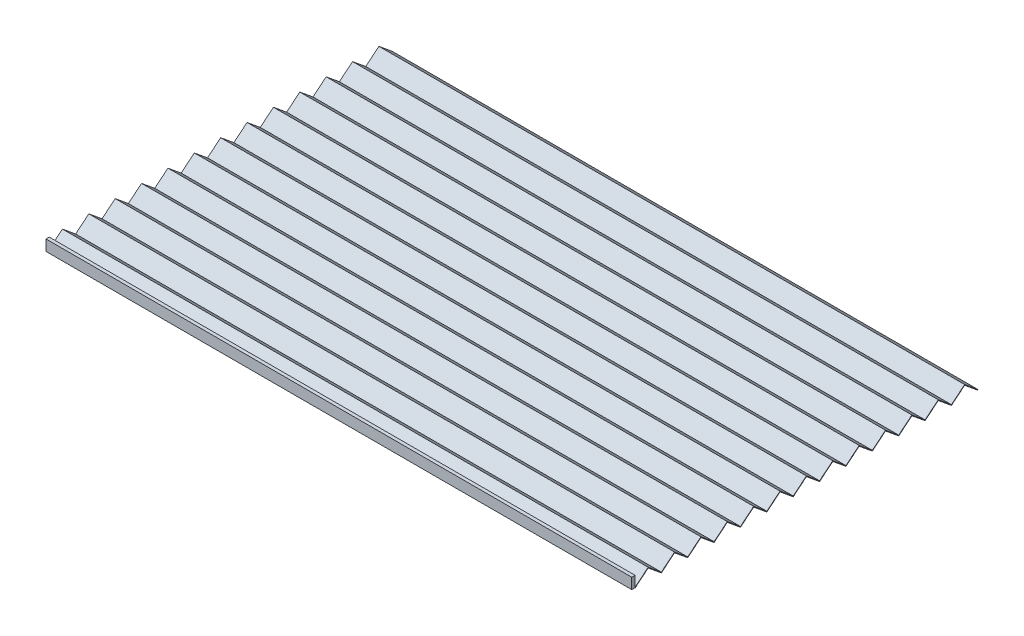
SolidWorks part; units mm, degrees
ref_plane "Front Plane" through (0, 0, 0) normal (0, 0, 1) x (1, 0, 0)
ref_plane "Top Plane" through (0, 0, 0) normal (0, 1, 0) x (1, 0, 0)
ref_plane "Right Plane" through (0, 0, 0) normal (1, 0, 0) x (0, 0, -1)
sketch "Sketch2" plane through (0, 0, 0) normal (0, 0, 1) x (1, 0, 0)
  line L1 (-270, 10) -> (270, 10)
  line L2 (-270, 10) -> (-270, 0)
  line L3 (-270, 0) -> (270, 0)
  line L4 (270, 10) -> (270, 0)
  point P4 (0, 0)
  dimension "D1" = 10
  dimension "D2" = 540
extrude "Boss-Extrude1" add sketch "Sketch2" along normal blind 3
sketch "Sketch3" plane through (270, 0, 0) normal (1, 0, 0) x (0, 0, -1)
  line L0 (0, 10) -> (316.0681, 10) construction
  line L1 (0, 0) -> (316.0681, 0) construction
  line L2 (316.0681, 10) -> (316.0681, 0) construction
  line L3 (0, 0) -> (12.1565, 10)
  line L4 (12.1565, 10) -> (24.3129, 0)
  line L5 (24.3129, 0) -> (36.4694, 10)
  line L6 (36.4694, 10) -> (48.6259, 0)
  line L7 (48.6259, 0) -> (60.7823, 10)
  line L8 (60.7823, 10) -> (72.9388, 0)
  line L9 (72.9388, 0) -> (85.0953, 10)
  line L10 (85.0953, 10) -> (97.2517, 0)
  line L11 (97.2517, 0) -> (109.4082, 10)
  line L12 (109.4082, 10) -> (121.5647, 0)
  line L13 (121.5647, 0) -> (133.7211, 10)
  line L14 (133.7211, 10) -> (145.8776, 0)
  line L15 (145.8776, 0) -> (158.0341, 10)
  line L16 (158.0341, 10) -> (170.1905, 0)
  line L17 (170.1905, 0) -> (182.347, 10)
  line L18 (182.347, 10) -> (194.5035, 0)
  line L20 (194.5035, 0) -> (206.6599, 10)
  line L21 (206.6599, 10) -> (218.8164, 0)
  line L22 (218.8164, 0) -> (230.9729, 10)
  line L23 (230.9729, 10) -> (243.1293, 0)
  line L24 (243.1293, 0) -> (255.2858, 10)
  line L25 (255.2858, 10) -> (267.4422, 0)
  line L26 (267.4422, 0) -> (279.5987, 10)
  line L27 (279.5987, 10) -> (291.7552, 0)
  line L28 (291.7552, 0) -> (303.9116, 10)
  line L29 (303.9116, 10) -> (316.0681, 0)
  line L30 (316.0681, 10) -> (316.0681, 0) construction
extrude "Extrude-Thin1" add sketch "Sketch3" against normal through all thin thin type mid plane wall 0.5
